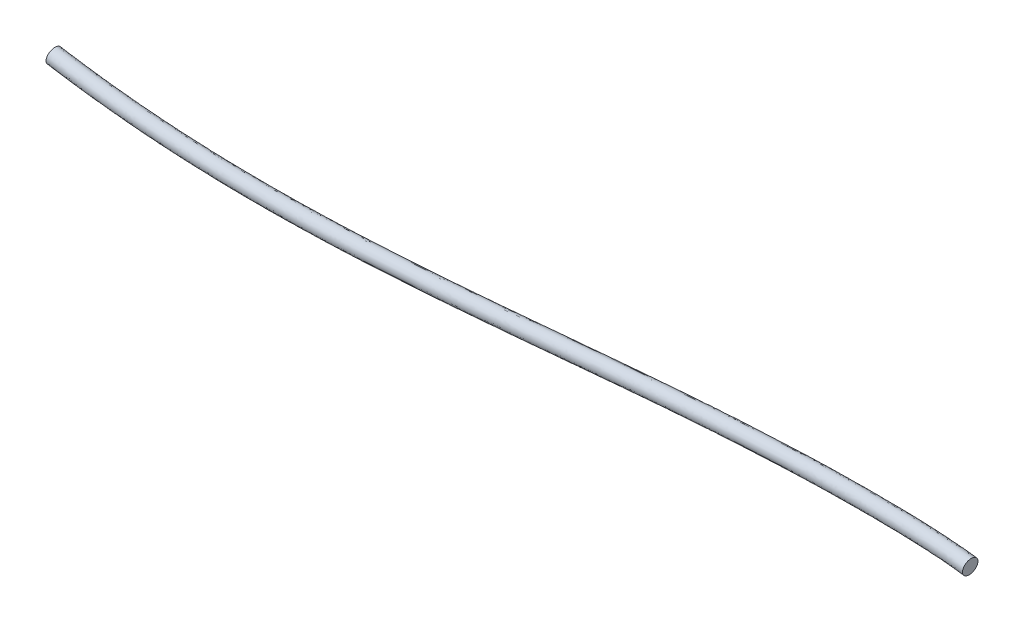
SolidWorks part; units mm, degrees
ref_plane "Front Plane" through (0, 0, 0) normal (0, 0, 1) x (1, 0, 0)
ref_plane "Top Plane" through (0, 0, 0) normal (0, 1, 0) x (1, 0, 0)
ref_plane "Right Plane" through (0, 0, 0) normal (1, 0, 0) x (0, 0, -1)
sketch "Sketch1" plane through (0, 0, 0) normal (0, 0, 1) x (1, 0, 0)
  spline S0 degree 3 poles (-45.0249, 7.078) (-26.6796, 4.0351) (-6.8897, 9.1168) (13.0068, 8.2854) (14.5423, 8.0781) knots 0 0 0 0 0.922189 1 1 1 1
sweep "Sweep1" add path "Sketch1" circular profile diameter 1 parameters "D3"=1
